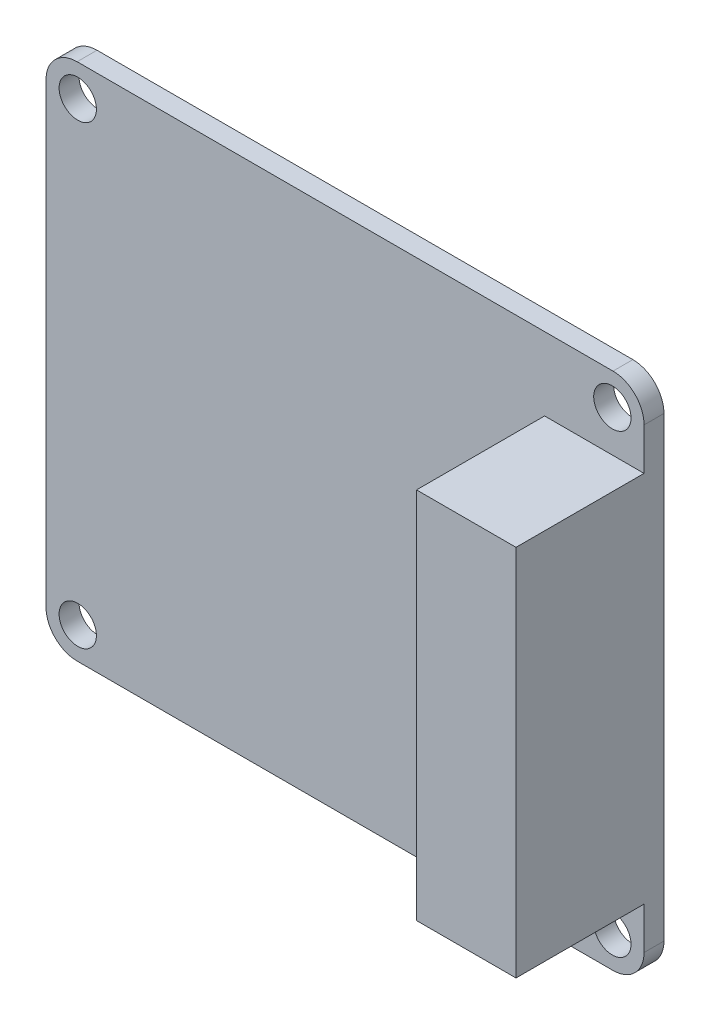
SolidWorks part; units mm, degrees
ref_plane "Front Plane" through (0, 0, 0) normal (1, 0, 0) x (0, 1, 0)
ref_plane "Top Plane" through (0, 0, 0) normal (0, 0, 1) x (0, 1, 0)
ref_plane "Right Plane" through (0, 0, 0) normal (0, 1, 0) x (-1, 0, 0)
sketch "Sketch1" plane through (0, 0, 0) normal (0, 0, 1) x (0, 1, 0)
  line L0 (2.5499, 2.5499) -> (39.2001, 45.5501) construction
  line L1 (2.5, 0) -> (39.25, 0)
  line L2 (0, 2.5) -> (0, 45.6)
  line L3 (2.5, 48.1) -> (39.25, 48.1)
  line L4 (41.75, 2.5) -> (41.75, 45.6)
  line L5 (39.2001, 45.5501) -> (39.2001, 48.1) construction
  line L6 (39.2001, 45.5501) -> (41.75, 45.5501) construction
  line L8 (35.875, 0) -> (5.875, 0)
  line L9 (35.875, 0) -> (35.875, 8)
  line L10 (35.875, 8) -> (5.875, 8)
  line L11 (5.875, 0) -> (5.875, 8)
  circle A0 centre (2.5499, 2.5499) radius 1.5
  circle A1 centre (39.2001, 45.5501) radius 1.5
  circle A2 centre (2.5499, 45.5501) radius 1.5
  circle A3 centre (39.2001, 2.5499) radius 1.5
  arc A4 (2.5, 0) -> (0, 2.5) centre (2.5, 2.5) cw
  arc A5 (39.25, 0) -> (41.75, 2.5) centre (39.25, 2.5) ccw
  arc A6 (0, 45.6) -> (2.5, 48.1) centre (2.5, 45.6) cw
  arc A7 (39.25, 48.1) -> (41.75, 45.6) centre (39.25, 45.6) cw
  point P13 (20.875, 24.05)
  point P14 (41.75, 24.05)
  point P15 (20.875, 0)
  point P20 (0, 0)
  point P23 (41.75, 0)
  point P26 (0, 48.1)
  point P29 (41.75, 48.1)
  point P34 (35.189, 8)
  point P35 (57.5971, 8)
  dimension "D3" = 56.5
  dimension "D4" = 3
  dimension "D5" = 2.5
  dimension "D1" = 41.75
  dimension "D2" = 48.1
  dimension "D6" = 8
  dimension "D7" = 30
extrude "Boss-Extrude1" add sketch "Sketch1" along normal blind 1.6 contours A7 L3 A6 L2 A4 L1 L11 L10 L9 A5 L4 A3 A2 A1 A0 | L11 L1 L9 L10 region at (-26.8242, 20.875, 0) region at (-4, 20.875, 0)
extrude "Boss-Extrude2" add sketch "Sketch1<3>" along normal blind 11.9 contours L11 L1 L9 L10 region at (-4, 20.875, 0)
sketch "Sketch1<3>" plane through (0, 0, 0) normal (0, 0, 1) x (0, 1, 0) same geometry as "Sketch1"
